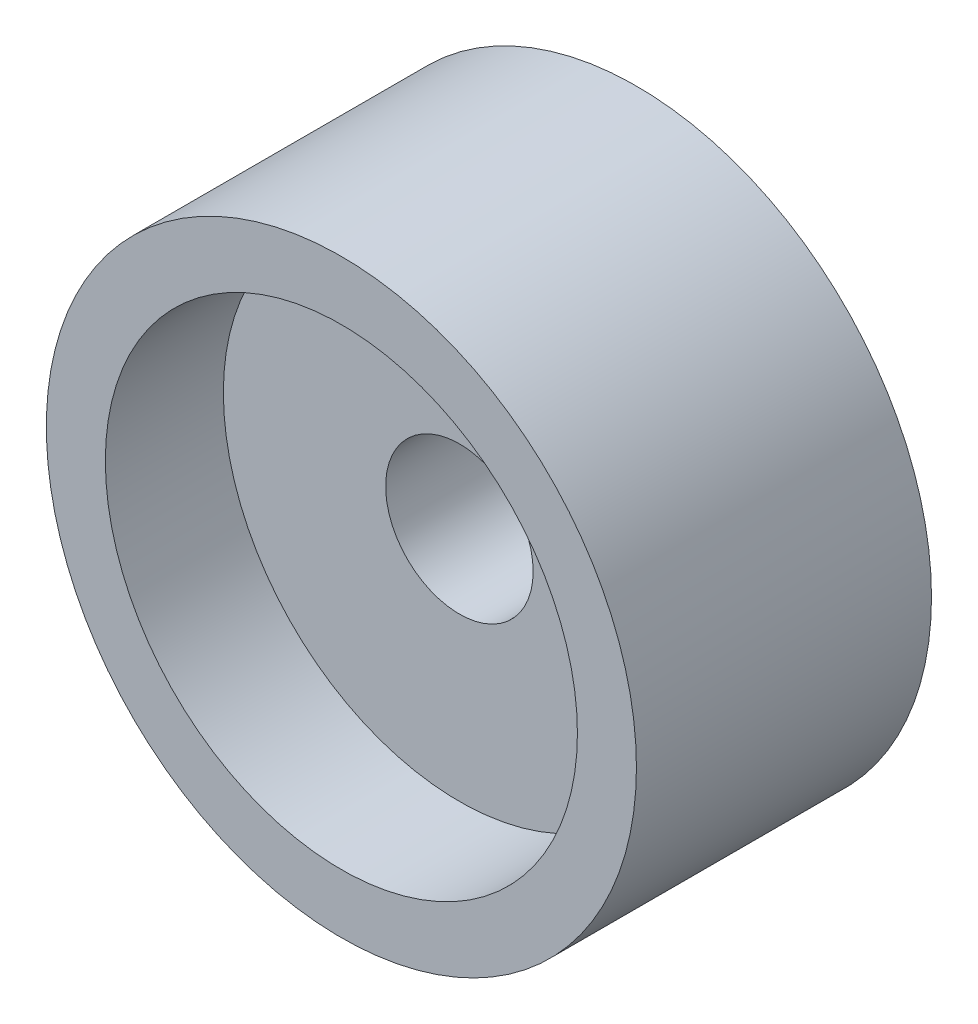
SolidWorks part; units mm, degrees
ref_plane "Front Plane" through (0, 0, 0) normal (0, 0, 1) x (1, 0, 0)
ref_plane "Top Plane" through (0, 0, 0) normal (0, 1, 0) x (1, 0, 0)
ref_plane "Right Plane" through (0, 0, 0) normal (1, 0, 0) x (0, 0, -1)
sketch "Sketch1" plane through (0, 0, 0) normal (0, 0, 1) x (1, 0, 0)
  circle A0 centre (0, 0) radius 5
  circle A1 centre (0, 0) radius 4
  circle A2 centre (0, 0) radius 1.25
  dimension "D1" = 2.5
  dimension "D2" = 8
  dimension "D3" = 1
extrude "Boss-Extrude1" add sketch "Sketch1" along normal blind 2 contours A0 A1 region at (-4.8586, 0, 0)
extrude "Boss-Extrude2" add sketch "Sketch1<3>" against normal blind 3 contours A1 A2 | A0 A1 region at (-4.8586, 0, 0) region at (-3.8869, 0, 0)
sketch "Sketch1<3>" plane through (0, 0, 0) normal (0, 0, 1) x (1, 0, 0) same geometry as "Sketch1"
